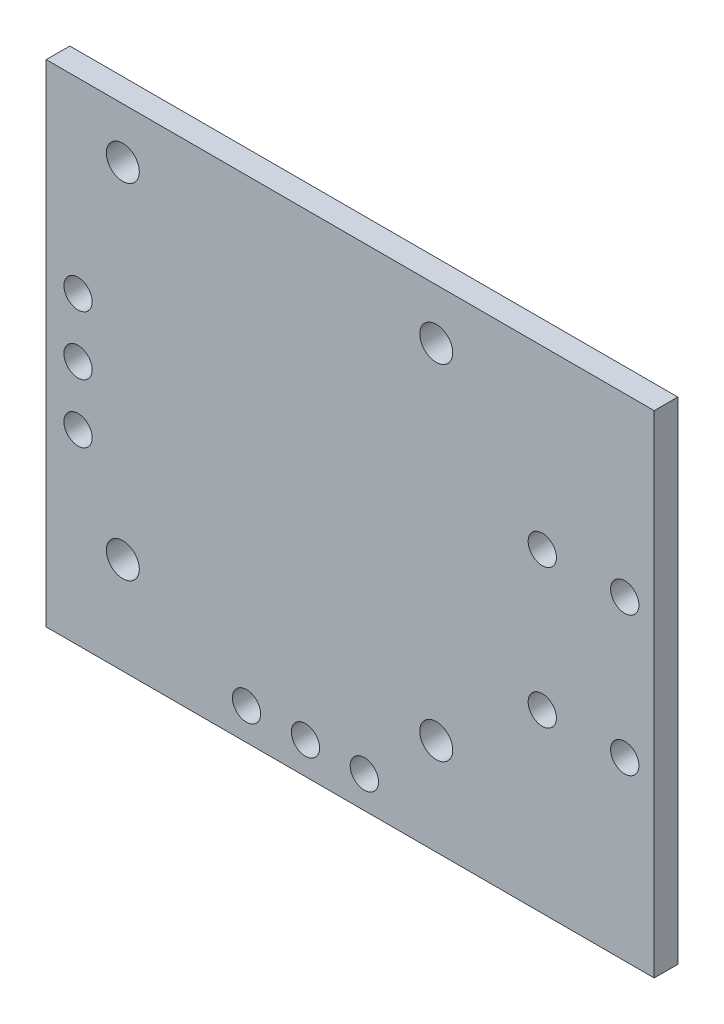
SolidWorks part; units mm, degrees
ref_plane "正面" through (0, 0, 0) normal (0, 0, 1) x (1, 0, 0)
ref_plane "平面" through (0, 0, 0) normal (0, 1, 0) x (1, 0, 0)
ref_plane "右側面" through (0, 0, 0) normal (1, 0, 0) x (0, 0, -1)
sketch "ｽｹｯﾁ1" plane through (0, 0, 0) normal (0, 0, 1) x (1, 0, 0)
  line L0 (0, -10.425) -> (25.8, -10.425) construction
  line L1 (0, 0) -> (25.8, 0)
  line L2 (0, 0) -> (0, -20.85)
  line L3 (0, -20.85) -> (25.8, -20.85)
  line L4 (25.8, 0) -> (25.8, -20.85)
  line L5 (1.35, -20.85) -> (1.35, 0) construction
  line L6 (25.8, -2.15) -> (0, -2.15) construction
  line L7 (21.05, -7.475) -> (24.55, -7.475) construction
  line L8 (21.05, -7.475) -> (21.05, -13.375) construction
  line L9 (21.05, -13.375) -> (24.55, -13.375) construction
  line L10 (24.55, -7.475) -> (24.55, -13.375) construction
  line L11 (25.8, -16.75) -> (0, -16.75) construction
  line L12 (16.55, -20.85) -> (16.55, 0) construction
  line L13 (3.25, 0) -> (3.25, -20.85) construction
  line L16 (8.5, -19.5) -> (25.8, -19.5) construction
  circle A0 centre (1.35, -7.925) radius 0.6
  circle A1 centre (1.35, -10.425) radius 0.6
  circle A2 centre (1.35, -12.925) radius 0.6
  circle A3 centre (3.25, -16.75) radius 0.7
  circle A4 centre (3.25, -2.15) radius 0.7
  circle A5 centre (16.55, -2.15) radius 0.7
  circle A6 centre (16.55, -16.75) radius 0.7
  circle A7 centre (8.5, -19.5) radius 0.6
  circle A8 centre (11, -19.5) radius 0.6
  circle A9 centre (8.5, -19.5) radius 0.6
  circle A10 centre (21.05, -7.475) radius 0.6
  circle A11 centre (24.55, -7.475) radius 0.6
  circle A12 centre (21.05, -13.375) radius 0.6
  circle A13 centre (24.55, -13.375) radius 0.6
  circle A14 centre (13.5, -19.5) radius 0.6
  dimension "D3" = 1.2
  dimension "D4" = 1.2
  dimension "D8" = 1.4
  dimension "D16" = 1.2
  dimension "D1" = 20.85
  dimension "D2" = 25.8
  dimension "D5" = 5.9
  dimension "D6" = 3.5
  dimension "D7" = 4.75
  dimension "D9" = 2.5
  dimension "D10" = 1.35
  dimension "D11" = 2.15
  dimension "D12" = 1.35
  dimension "D13" = 4.1
  dimension "D14" = 2.5
  dimension "D15" = 8.5
  dimension "D17" = 13.3
  dimension "D18" = 3.25
  dimension "D19" = 2.5
extrude "ﾎﾞｽ - 押し出し1" add sketch "ｽｹｯﾁ1" along normal blind 1 contours L4 L1 L2 L3 A13 A12 A11 A10 A8 A7 A6 A5 A4 A3 A2 A1 A0 region at (12.9371, -10.3774, 0)
